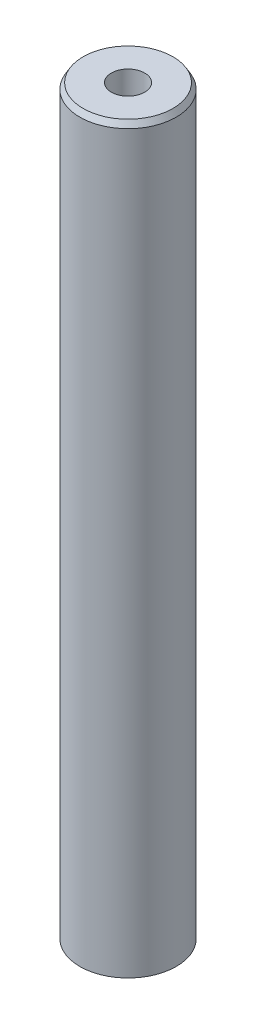
SolidWorks part; units mm, degrees
ref_plane "Front Plane" through (0, 0, 0) normal (0, 0, 1) x (1, 0, 0)
ref_plane "Top Plane" through (0, 0, 0) normal (0, 1, 0) x (1, 0, 0)
ref_plane "Right Plane" through (0, 0, 0) normal (1, 0, 0) x (0, 0, -1)
sketch "Sketch1" plane through (0, 0, 0) normal (0, 1, 0) x (1, 0, 0)
  circle A0 centre (0, 0) radius 15
  dimension "SHAFT_OD" = 30
extrude "Boss-Extrude1" add sketch "Sketch1" along normal blind 231.6195
sketch "Sketch2" plane through (0, 0, 0) normal (0, 1, 0) x (1, 0, 0)
  circle A0 centre (0, 0) radius 5.1811
  dimension "BORE_D" = 10.3621
extrude "Cut-Extrude1" cut sketch "Sketch2" along normal through all
chamfer "Chamfer1" distance 1.8112 angle 30 2 edges at (0, 231.6195, 15) (0, 0, 15) first distance on face at (0, 231.6195, 15) first distance on face at (0, 0, 5.1811)
